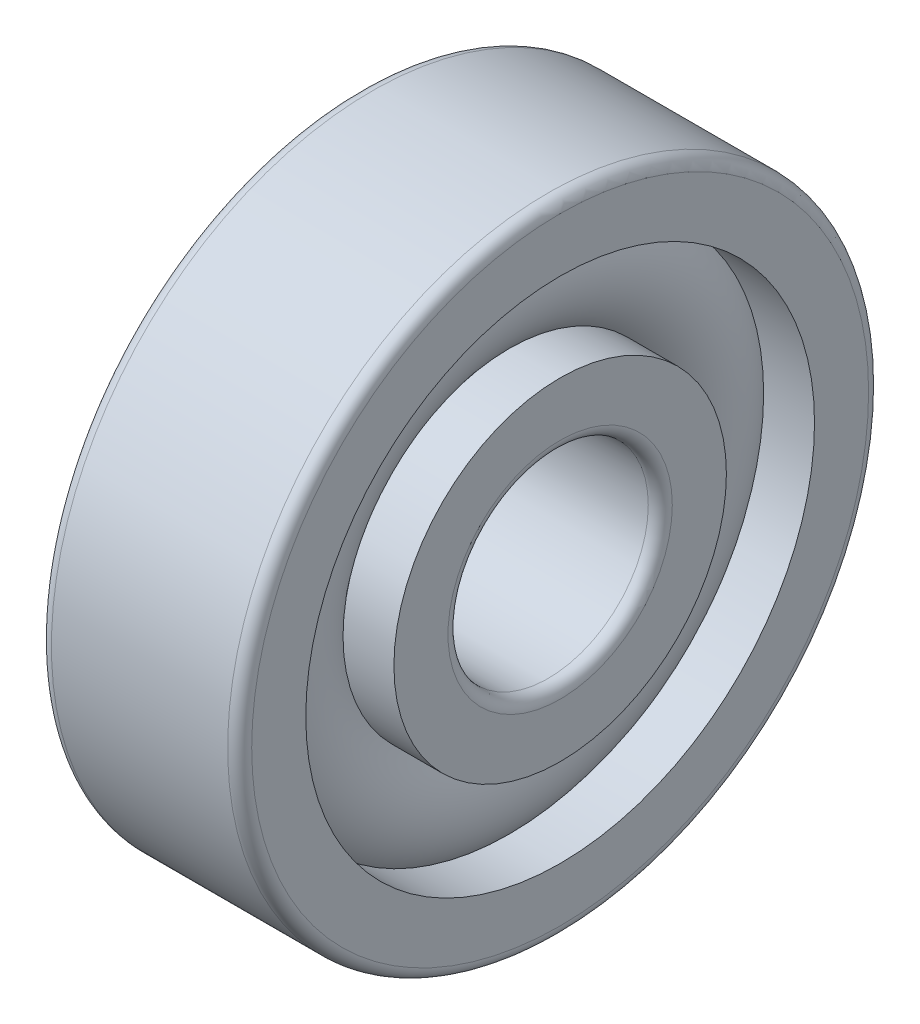
SolidWorks part; units mm, degrees
ref_plane "Plane1" through (0, 0, 0) normal (0, 0, 1) x (1, 0, 0)
ref_plane "Plane2" through (0, 0, 0) normal (0, 1, 0) x (1, 0, 0)
ref_plane "Plane3" through (0, 0, 0) normal (1, 0, 0) x (0, 0, -1)
sketch "Clipboard" plane through (0, 0, 0) normal (0, 0, 1) x (1, 0, 0)
  line L0 (-10, 0) -> (10, 0) construction
  line L1 (0, 0) -> (22.3471, -0.7804)
  line L2 (0, 0) -> (5.2468, 0.1832)
  line L3 (0, 0) -> (22.3471, -0.7804)
  line L4 (0, 0) -> (-22.3573, -0.3902)
sketch "CagSpiSke" plane through (0, 0, 0) normal (0, 0, 1) x (1, 0, 0)
  line L0 (0.165, 4.975) -> (0.165, 5.525)
  line L1 (0.165, 5.525) -> (-0.165, 5.525)
  line L2 (-0.165, 5.525) -> (-0.165, 4.975)
  line L3 (-0.165, 4.975) -> (0.165, 4.975)
  line L4 (-20.6375, 0) -> (20.6375, 0) construction
  line L5 (0, 0) -> (0, 23.7692) construction
revolve "CageSpine" add sketch "CagSpiSke" angle 0.001 about L4 reverse direction yes
ref_axis "Axis1" through (-50, 0, 0) along (1, 0, 0)
sketch "CagBalSke" plane through (0, 0, 0) normal (0, 0, 1) x (1, 0, 0)
  line L0 (-1.815, 5.25) -> (1.815, 5.25)
  line L1 (-1.905, 5.25) -> (1.905, 5.25) construction
  line L2 (-10, 0) -> (10, 0) construction
  line L3 (0, 0) -> (0, 24) construction
  arc A0 (1.815, 5.25) -> (-1.815, 5.25) centre (0, 5.25) cw
revolve "CageBall" [suppressed] add sketch "CagBalSke" angle 360 about L1 reverse direction yes
pattern_circular "CageBalls" [suppressed] count 2 every 180 about axis through (-50, 0, 0) along (1, 0, 0)
sketch "CagTrmODSke" plane through (0, 0, 0) normal (0, 0, 1) x (1, 0, 0)
  line L0 (1.816, 5.525) -> (1.816, 7.066)
  line L1 (1.816, 7.066) -> (-1.816, 7.066)
  line L2 (-1.816, 7.066) -> (-1.816, 5.525)
  line L3 (-1.816, 5.525) -> (1.816, 5.525)
  line L4 (-20.6375, 0) -> (20.6375, 0) construction
  line L5 (0, 0) -> (0, 25) construction
revolve "CageTrimOD" [suppressed] cut sketch "CagTrmODSke" angle 360 about L4 reverse direction yes
sketch "CagTrmIDSke" plane through (0, 0, 0) normal (0, 0, 1) x (1, 0, 0)
  line L0 (1.816, 3.436) -> (1.816, 4.975)
  line L1 (1.816, 4.975) -> (-1.816, 4.975)
  line L2 (-1.816, 4.975) -> (-1.816, 3.436)
  line L3 (-1.816, 3.436) -> (1.816, 3.436)
  line L4 (-20.6375, 0) -> (20.6375, 0) construction
  line L5 (0, 0) -> (0, 25) construction
revolve "CageTrimID" [suppressed] cut sketch "CagTrmIDSke" angle 360 about L4 reverse direction yes
sketch "BalSimSke" plane through (0, 0, 0) normal (0, 0, 1) x (1, 0, 0)
  line L0 (-10, 0) -> (10, 0) construction
  line L1 (-10, 5.25) -> (10, 5.25) construction
  line L2 (0, 0) -> (0, 23) construction
  circle A0 centre (0, 5.25) radius 1.65
revolve "BallsSimplified" add sketch "BalSimSke" angle 360 about L0
sketch "BalDetSke" plane through (0, 0, 0) normal (0, 0, 1) x (1, 0, 0)
  line L0 (-1.65, 5.25) -> (1.65, 5.25)
  line L1 (-1.905, 5.25) -> (1.905, 5.25) construction
  line L2 (0, 0) -> (0, 25) construction
  arc A0 (1.65, 5.25) -> (-1.65, 5.25) centre (0, 5.25) cw
revolve "BallDetailed" [suppressed] add sketch "BalDetSke" angle 360 about L1 reverse direction yes
sketch "InnRacSke" plane through (0, 0, 0) normal (0, 0, 1) x (1, 0, 0)
  line L0 (-1.1961, 4.15) -> (-2.5, 4.15)
  line L1 (-2.5, 4.15) -> (-2.5, 2.8)
  line L2 (-2.2, 2.5) -> (2.2, 2.5)
  line L3 (2.5, 2.8) -> (2.5, 4.15)
  line L4 (2.5, 4.15) -> (1.1961, 4.15)
  line L5 (-20.6375, 0) -> (20.6375, 0) construction
  line L6 (0, 0) -> (0, 30) construction
  arc A0 (-2.5, 2.8) -> (-2.2, 2.5) centre (-2.2, 2.8) ccw
  arc A1 (2.2, 2.5) -> (2.5, 2.8) centre (2.2, 2.8) ccw
  arc A2 (1.1961, 4.15) -> (-1.1961, 4.15) centre (0, 5.25) cw
revolve "InnerRace" add sketch "InnRacSke" angle 360 about L5 reverse direction yes
sketch "OutRacSke" plane through (0, 0, 0) normal (0, 0, 1) x (1, 0, 0)
  line L0 (-1.1961, 6.35) -> (-2.5, 6.35)
  line L1 (-2.5, 6.35) -> (-2.5, 7.7)
  line L2 (-2.2, 8) -> (2.2, 8)
  line L3 (2.5, 7.7) -> (2.5, 6.35)
  line L4 (2.5, 6.35) -> (1.1961, 6.35)
  line L5 (-20.6375, 0) -> (20.6375, 0) construction
  line L6 (0, 0) -> (0, 30) construction
  arc A0 (-2.5, 7.7) -> (-2.2, 8) centre (-2.2, 7.7) cw
  arc A1 (2.2, 8) -> (2.5, 7.7) centre (2.2, 7.7) cw
  arc A2 (1.1961, 6.35) -> (-1.1961, 6.35) centre (0, 5.25) ccw
revolve "OuterRace" add sketch "OutRacSke" angle 360 about L5 reverse direction yes
pattern_circular "BallsDetailed" [suppressed] count 2 every 180 about axis through (-50, 0, 0) along (1, 0, 0)
equation "\"BallCLRad@Clipboard\" = ( \"OD@OutRacSke\" + \"ID@InnRacSke\" ) / 4"
equation "\"BallCLRad@BalSimSke\" = \"BallCLRad@Clipboard\""
equation "\"BallCLRad@BalDetSke\" = \"BallCLRad@Clipboard\""
equation "\"BallCLRad@InnRacSke\" = \"BallCLRad@Clipboard\""
equation "\"BallCLRad@OutRacSke\" = \"BallCLRad@Clipboard\""
equation "\"Ball_diameter@InnRacSke\" = \"Ball_diameter@BalDetSke\" - 0.05"
equation "\"Ball_diameter@OutRacSke\" = \"Ball_diameter@BalDetSke\" - 0.05"
equation "\"Ball_diameter@BalSimSke\" = \"Ball_diameter@BalDetSke\""
equation "\"Width@OutRacSke\" = \"Width@InnRacSke\""
equation "\"Fillet_radius@OutRacSke\" = \"Fillet_radius@InnRacSke\""
equation "\"Max_count@Clipboard\" = int( 3.14159265 / atn(( \"Ball_diameter@BalDetSke\" / 2) / sqr( \"BallCLRad@Clipboard\"  *  \"BallCLRad@Clipboard\" - ( \"Ball_diameter@BalDetSke\" / 2) *  ( \"Ball_diameter@BalDetSke\" / 2))))"
equation "\"Max_count@Clipboard\" = ((sgn( \"Max_count@Clipboard\" - \"Count@Clipboard\" )-1)*( \"Max_count@Clipboard\" - \"Count@Clipboard\" ))/-2+ \"Count@Clipboard\""
equation "\"Count@BallsDetailed\" = int( \"Show_count@Clipboard\" ) "
equation "\"Count@BallsDetailed\" = ((sgn( \"Count@BallsDetailed\" - \"Max_count@Clipboard\" )-1)*( \"Count@BallsDetailed\" - \"Max_count@Clipboard\" ))/-2+ \"Max_count@Clipboard\""
equation "\"Count@BallsDetailed\" = ((sgn( \"Count@BallsDetailed\" - \"Min_count@Clipboard\" )+1)*( \"Count@BallsDetailed\" - \"Min_count@Clipboard\"))/2 +\"Min_count@Clipboard\""
equation "\"Angle@BallsDetailed\" = 360.0 / \"Max_count@Clipboard\""
equation "\"BallCLRad@CagBalSke\" = \"BallCLRad@Clipboard\""
equation "\"Count@CageBalls\" = \"Count@BallsDetailed\""
equation "\"Angle@CageBalls\" = \"Angle@BallsDetailed\""
equation "\"Angle@CageSpine\" =  \"Angle@CageBalls\" * ( \"Count@CageBalls\" -1 + int( \"Count@CageBalls\" / \"Max_count@Clipboard\" ) )  + 0.001 -  int( \"Count@CageBalls\" / \"Max_count@Clipboard\" ) * 0.001"
equation "\"Angle@CageSpine\" =  \"Angle@CageSpine\" * int( \"Min_count@Clipboard\" / 2) + int(1 / \"Min_count@Clipboard\")  * 0.001"
equation "\"CageWallOD@CagBalSke\" =  \"Ball_diameter@BalDetSke\" * 1.1"
equation "\"Thickness@CagSpiSke\" =  \"Ball_diameter@BalDetSke\" * 0.1"
equation "\"OD@CagTrmODSke\" = \"BallCLRad@Clipboard\" * 2 + \"CageWallOD@CagBalSke\" + 0.002"
equation "\"ID@CagTrmODSke\" = \"BallCLRad@Clipboard\" * 2 + \"Ball_diameter@BalDetSke\" / 6"
equation "\"OD@CagTrmIDSke\" = \"BallCLRad@Clipboard\" * 2 - \"Ball_diameter@BalDetSke\" / 6"
equation "\"ID@CagTrmIDSke\" = \"BallCLRad@Clipboard\" * 2 - \"CageWallOD@CagBalSke\" + 0.002"
equation "\"OD@CagSpiSke\" = \"ID@CagTrmODSke\""
equation "\"ID@CagSpiSke\" = \"OD@CagTrmIDSke\""
equation "\"Width@CagTrmODSke\" = \"CageWallOD@CagBalSke\" + 0.002"
equation "\"Width@CagTrmIDSke\" = \"CageWallOD@CagBalSke\" + 0.002"
